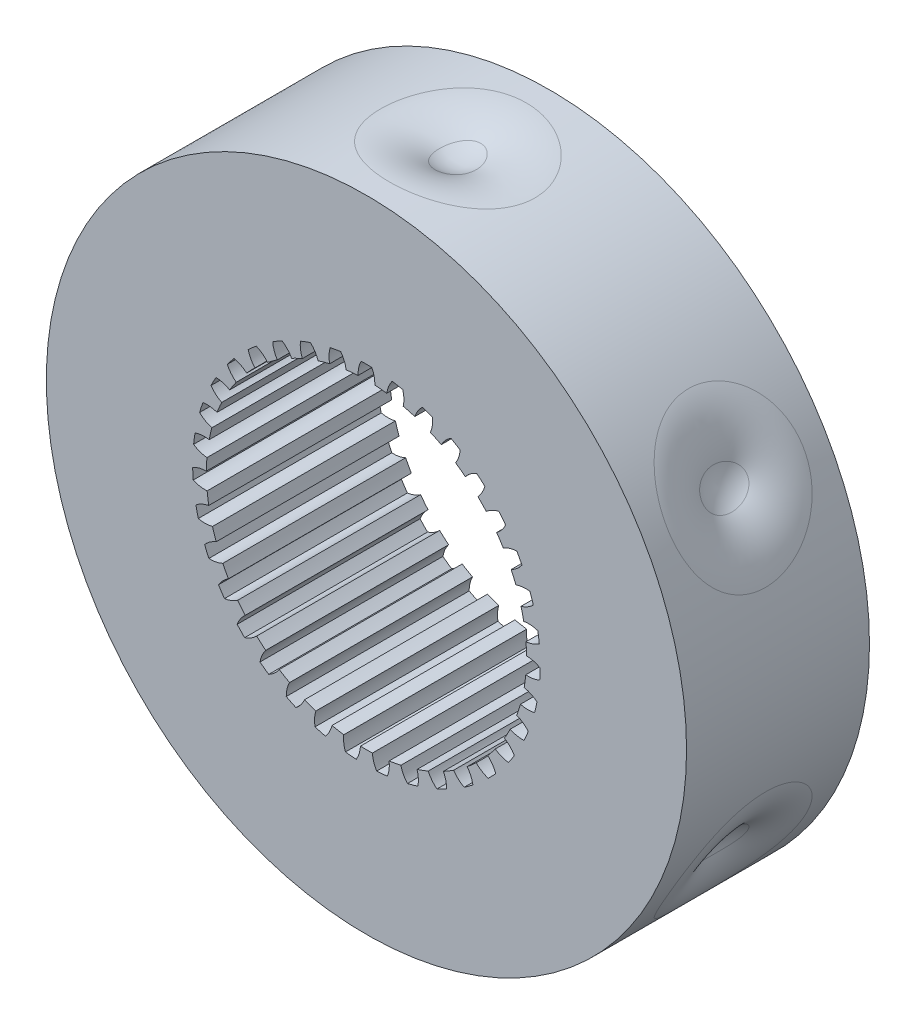
SolidWorks part; units mm, degrees
ref_plane "Front Plane" through (0, 0, 0) normal (0, 0, 1) x (1, 0, 0)
ref_plane "Top Plane" through (0, 0, 0) normal (0, 1, 0) x (1, 0, 0)
ref_plane "Right Plane" through (0, 0, 0) normal (1, 0, 0) x (0, 0, -1)
sketch "Sketch1" plane through (0, 0, 0) normal (0, 0, 1) x (1, 0, 0)
  circle A0 centre (0, 0) radius 35
  dimension "D1" = 70
extrude "Boss-Extrude1" add sketch "Sketch1" along normal mid plane 20
sketch "Sketch2" plane through (0, 0, 0) normal (0, 0, 1) x (1, 0, 0)
  line L0 (0, 0) -> (0, 38.6645) construction
  line L1 (0, 33) -> (0, 43)
  arc A0 (0, 33) -> (0, 43) centre (0, 38) ccw
  dimension "D2" = 10
  dimension "D1" = 38
revolve "Cut-Revolve1" cut sketch "Sketch2" angle 360 about L0
fillet "Fillet1" radius 10 1 edges at (-3.7349, 34.8001, -0.9006)
sketch "Sketch3" plane through (0, 0, -10) normal (0, 0, -1) x (-1, 0, 0)
  line L0 (0, 0) -> (0, 19.9196) construction
  arc A0 (-0.9159, 17.476) -> (-2.2193, 17.3587) centre (0, 0) ccw
  arc A1 (0.5906, 18.9908) -> (-0.5906, 18.9908) centre (0, 0) ccw
  arc A4 (-0.9159, 17.476) -> (-0.5906, 18.9908) centre (2.2552, 17.5875) cw
  arc A5 (0.9159, 17.476) -> (0.5906, 18.9908) centre (-2.2552, 17.5875) ccw
  arc A6 (3.9721, 18.5802) -> (2.8098, 18.7911) centre (0, 0) ccw
  arc A7 (2.2193, 17.3587) -> (2.8098, 18.7911) centre (5.3593, 16.9022) cw
  arc A8 (2.2193, 17.3587) -> (0.9159, 17.476) centre (0, 0) ccw
  arc A9 (4.0216, 17.0316) -> (3.9721, 18.5802) centre (0.9214, 17.7075) ccw
  arc A10 (7.2259, 17.5723) -> (6.1199, 17.9874) centre (0, 0) ccw
  arc A11 (5.2832, 16.6835) -> (6.1199, 17.9874) centre (8.2912, 15.6736) cw
  arc A12 (5.2832, 16.6835) -> (0, 17.5) centre (0, 0) ccw
  arc A13 (6.9981, 16.0398) -> (7.2259, 17.5723) centre (4.0684, 17.2584) ccw
  arc A14 (10.2474, 15.9997) -> (9.2333, 16.6056) centre (0, 0) ccw
  arc A15 (8.1772, 15.472) -> (9.2333, 16.6056) centre (10.9566, 13.9413) cw
  arc A16 (8.1772, 15.472) -> (-5.2832, 16.6835) centre (0, 0) ccw
  arc A17 (9.7497, 14.5325) -> (10.2474, 15.9997) centre (7.0846, 16.2547) ccw
  arc A18 (12.9396, 13.9128) -> (12.05, 14.6901) centre (0, 0) ccw
  arc A19 (10.8084, 13.7633) -> (12.05, 14.6901) centre (13.2698, 11.7608) cw
  arc A20 (10.8084, 13.7633) -> (-5.2832, 16.6835) centre (0, 0) ccw
  arc A21 (12.1879, 12.5581) -> (12.9396, 13.9128) centre (9.8731, 14.7284) ccw
  arc A22 (15.2159, 11.3788) -> (14.4794, 12.3024) centre (0, 0) ccw
  arc A23 (13.0923, 11.6122) -> (14.4794, 12.3024) centre (15.1566, 9.2024) cw
  arc A24 (13.0923, 11.6122) -> (-5.2832, 16.6835) centre (0, 0) ccw
  arc A25 (14.2343, 10.1801) -> (15.2159, 11.3788) centre (12.3443, 12.7288) ccw
  arc A26 (17.0031, 8.479) -> (16.4433, 9.5193) centre (0, 0) ccw
  arc A27 (14.9553, 9.0879) -> (16.4433, 9.5193) centre (16.5561, 6.3482) cw
  arc A28 (14.9553, 9.0879) -> (15.8233, 7.4748) centre (0, 0) ccw
  arc A29 (15.8233, 7.4748) -> (17.0031, 8.479) centre (14.4188, 10.3201) ccw
  arc A30 (18.2439, 5.3067) -> (17.8788, 6.4302) centre (0, 0) ccw
  arc A31 (16.3377, 6.2714) -> (17.8788, 6.4302) centre (17.4236, 3.29) cw
  arc A32 (16.3377, 6.2714) -> (16.9037, 4.5293) centre (0, 0) ccw
  arc A33 (16.9037, 4.5293) -> (18.2439, 5.3067) centre (16.0298, 7.5797) ccw
  arc A34 (18.8982, 1.9639) -> (18.7397, 3.1345) centre (0, 0) ccw
  arc A35 (17.1949, 3.2535) -> (18.7397, 3.1345) centre (17.731, 0.126) cw
  arc A36 (17.1949, 3.2535) -> (17.4408, 1.4383) centre (0, 0) ccw
  arc A37 (17.4408, 1.4383) -> (18.8982, 1.9639) centre (17.1256, 4.5956) ccw
  arc A38 (18.9452, -1.4421) -> (18.9982, -0.262) centre (0, 0) ccw
  arc A39 (17.4995, 0.1309) -> (18.9982, -0.262) centre (17.4686, -3.042) cw
  arc A40 (17.4995, 0.1309) -> (17.4173, -1.699) centre (0, 0) ccw
  arc A41 (17.4173, -1.699) -> (18.9452, -1.4421) centre (17.671, 1.4639) ccw
  arc A42 (18.3832, -4.8017) -> (18.6461, -3.65) centre (0, 0) ccw
  arc A43 (17.2417, -2.9959) -> (18.6461, -3.65) centre (16.6447, -6.1123) cw
  arc A44 (17.2417, -2.9959) -> (16.8341, -4.7817) centre (0, 0) ccw
  arc A45 (16.8341, -4.7817) -> (18.3832, -4.8017) centre (17.6484, -1.7149) ccw
  arc A46 (17.2304, -8.007) -> (17.6947, -6.9207) centre (0, 0) ccw
  arc A47 (16.4296, -6.0263) -> (17.6947, -6.9207) centre (15.2858, -8.9861) cw
  arc A48 (16.4296, -6.0263) -> (15.7097, -7.7107) centre (0, 0) ccw
  arc A49 (15.7097, -7.7107) -> (17.2304, -8.007) centre (17.0585, -4.8386) ccw
  arc A50 (15.5238, -10.9549) -> (16.1746, -9.969) centre (0, 0) ccw
  arc A51 (15.0896, -8.8631) -> (16.1746, -9.969) centre (13.4357, -11.571) cw
  arc A52 (15.0896, -8.8631) -> (14.0805, -10.3919) centre (0, 0) ccw
  arc A53 (14.0805, -10.3919) -> (15.5238, -10.9549) centre (15.9204, -7.8067) ccw
  arc A54 (13.3183, -13.5508) -> (14.1346, -12.6969) centre (0, 0) ccw
  arc A55 (13.2645, -11.415) -> (14.1346, -12.6969) centre (11.1536, -13.7841) cw
  arc A56 (13.2645, -11.415) -> (11.9986, -12.739) centre (0, 0) ccw
  arc A57 (11.9986, -12.739) -> (13.3183, -13.5508) centre (14.2706, -10.524) ccw
  arc A58 (10.6847, -15.7111) -> (11.6404, -15.0167) centre (0, 0) ccw
  arc A59 (11.0131, -13.6001) -> (11.6404, -15.0167) centre (8.5132, -15.5542) cw
  arc A60 (11.0131, -13.6001) -> (9.5312, -14.6767) centre (0, 0) ccw
  arc A61 (9.5312, -14.6767) -> (10.6847, -15.7111) centre (12.1622, -12.903) ccw
  arc A62 (7.7076, -17.3664) -> (8.772, -16.8539) centre (0, 0) ccw
  arc A63 (8.4077, -15.348) -> (8.772, -16.8539) centre (5.599, -16.8243) cw
  arc A64 (8.4077, -15.348) -> (6.7574, -16.1427) centre (0, 0) ccw
  arc A65 (6.7574, -16.1427) -> (7.7076, -17.3664) centre (9.6628, -14.8673) ccw
  arc A66 (4.4829, -18.4636) -> (5.6216, -18.1493) centre (0, 0) ccw
  arc A67 (5.5321, -16.6026) -> (5.6216, -18.1493) centre (2.505, -17.5537) cw
  arc A68 (5.5321, -16.6026) -> (3.7664, -17.0899) centre (0, 0) ccw
  arc A69 (3.7664, -17.0899) -> (4.4829, -18.4636) centre (6.8529, -16.3537) ccw
  arc A70 (1.1141, -18.9673) -> (2.2906, -18.8614) centre (0, 0) ccw
  arc A71 (2.4787, -17.3236) -> (2.2906, -18.8614) centre (-0.6696, -17.7188) cw
  arc A72 (2.4787, -17.3236) -> (0.6543, -17.4878) centre (0, 0) ccw
  arc A73 (0.6543, -17.4878) -> (1.1141, -18.9673) centre (3.8227, -17.3145) ccw
  arc A74 (-2.2906, -18.8614) -> (-1.1141, -18.9673) centre (0, 0) ccw
  arc A75 (-0.6543, -17.4878) -> (-1.1141, -18.9673) centre (-3.8227, -17.3145) cw
  arc A76 (-0.6543, -17.4878) -> (-2.4787, -17.3236) centre (0, 0) ccw
  arc A77 (-2.4787, -17.3236) -> (-2.2906, -18.8614) centre (0.6696, -17.7188) ccw
  arc A78 (-5.6216, -18.1493) -> (-4.4829, -18.4636) centre (0, 0) ccw
  arc A79 (-3.7664, -17.0899) -> (-4.4829, -18.4636) centre (-6.8529, -16.3537) cw
  arc A80 (-3.7664, -17.0899) -> (-5.5321, -16.6026) centre (0, 0) ccw
  arc A81 (-5.5321, -16.6026) -> (-5.6216, -18.1493) centre (-2.505, -17.5537) ccw
  arc A82 (-8.772, -16.8539) -> (-7.7076, -17.3664) centre (0, 0) ccw
  arc A83 (-6.7574, -16.1427) -> (-7.7076, -17.3664) centre (-9.6628, -14.8673) cw
  arc A84 (-6.7574, -16.1427) -> (-8.4077, -15.348) centre (0, 0) ccw
  arc A85 (-8.4077, -15.348) -> (-8.772, -16.8539) centre (-5.599, -16.8243) ccw
  arc A86 (-11.6404, -15.0167) -> (-10.6847, -15.7111) centre (0, 0) ccw
  arc A87 (-9.5312, -14.6767) -> (-10.6847, -15.7111) centre (-12.1622, -12.903) cw
  arc A88 (-9.5312, -14.6767) -> (-11.0131, -13.6001) centre (0, 0) ccw
  arc A89 (-11.0131, -13.6001) -> (-11.6404, -15.0167) centre (-8.5132, -15.5542) ccw
  arc A90 (-14.1346, -12.6969) -> (-13.3183, -13.5508) centre (0, 0) ccw
  arc A91 (-11.9986, -12.739) -> (-13.3183, -13.5508) centre (-14.2706, -10.524) cw
  arc A92 (-11.9986, -12.739) -> (-13.2645, -11.415) centre (0, 0) ccw
  arc A93 (-13.2645, -11.415) -> (-14.1346, -12.6969) centre (-11.1536, -13.7841) ccw
  arc A94 (-16.1746, -9.969) -> (-15.5238, -10.9549) centre (0, 0) ccw
  arc A95 (-14.0805, -10.3919) -> (-15.5238, -10.9549) centre (-15.9204, -7.8067) cw
  arc A96 (-14.0805, -10.3919) -> (-15.0896, -8.8631) centre (0, 0) ccw
  arc A97 (-15.0896, -8.8631) -> (-16.1746, -9.969) centre (-13.4357, -11.571) ccw
  arc A98 (-17.6947, -6.9207) -> (-17.2304, -8.007) centre (0, 0) ccw
  arc A99 (-15.7097, -7.7107) -> (-17.2304, -8.007) centre (-17.0585, -4.8386) cw
  arc A100 (-15.7097, -7.7107) -> (-16.4296, -6.0263) centre (0, 0) ccw
  arc A101 (-16.4296, -6.0263) -> (-17.6947, -6.9207) centre (-15.2858, -8.9861) ccw
  arc A102 (-18.6461, -3.65) -> (-18.3832, -4.8017) centre (0, 0) ccw
  arc A103 (-16.8341, -4.7817) -> (-18.3832, -4.8017) centre (-17.6484, -1.7149) cw
  arc A104 (-16.8341, -4.7817) -> (-17.2417, -2.9959) centre (0, 0) ccw
  arc A105 (-17.2417, -2.9959) -> (-18.6461, -3.65) centre (-16.6447, -6.1123) ccw
  arc A106 (-18.9982, -0.262) -> (-18.9452, -1.4421) centre (0, 0) ccw
  arc A107 (-17.4173, -1.699) -> (-18.9452, -1.4421) centre (-17.671, 1.4639) cw
  arc A108 (-17.4173, -1.699) -> (-17.4995, 0.1309) centre (0, 0) ccw
  arc A109 (-17.4995, 0.1309) -> (-18.9982, -0.262) centre (-17.4686, -3.042) ccw
  arc A110 (-18.7397, 3.1345) -> (-18.8982, 1.9639) centre (0, 0) ccw
  arc A111 (-17.4408, 1.4383) -> (-18.8982, 1.9639) centre (-17.1256, 4.5956) cw
  arc A112 (-17.4408, 1.4383) -> (-17.1949, 3.2535) centre (0, 0) ccw
  arc A113 (-17.1949, 3.2535) -> (-18.7397, 3.1345) centre (-17.731, 0.126) ccw
  arc A114 (-17.8788, 6.4302) -> (-18.2439, 5.3067) centre (0, 0) ccw
  arc A115 (-16.9037, 4.5293) -> (-18.2439, 5.3067) centre (-16.0298, 7.5797) cw
  arc A116 (-16.9037, 4.5293) -> (-16.3377, 6.2714) centre (0, 0) ccw
  arc A117 (-16.3377, 6.2714) -> (-17.8788, 6.4302) centre (-17.4236, 3.29) ccw
  arc A118 (-16.4433, 9.5193) -> (-17.0031, 8.479) centre (0, 0) ccw
  arc A119 (-15.8233, 7.4748) -> (-17.0031, 8.479) centre (-14.4188, 10.3201) cw
  arc A120 (-15.8233, 7.4748) -> (-14.9553, 9.0879) centre (0, 0) ccw
  arc A121 (-14.9553, 9.0879) -> (-16.4433, 9.5193) centre (-16.5561, 6.3482) ccw
  arc A122 (-14.4794, 12.3024) -> (-15.2159, 11.3788) centre (0, 0) ccw
  arc A123 (-14.2343, 10.1801) -> (-15.2159, 11.3788) centre (-12.3443, 12.7288) cw
  arc A124 (-14.2343, 10.1801) -> (-13.0923, 11.6122) centre (0, 0) ccw
  arc A125 (-13.0923, 11.6122) -> (-14.4794, 12.3024) centre (-15.1566, 9.2024) ccw
  arc A126 (-12.05, 14.6901) -> (-12.9396, 13.9128) centre (0, 0) ccw
  arc A127 (-12.1879, 12.5581) -> (-12.9396, 13.9128) centre (-9.8731, 14.7284) cw
  arc A128 (-12.1879, 12.5581) -> (-10.8084, 13.7633) centre (0, 0) ccw
  arc A129 (-10.8084, 13.7633) -> (-12.05, 14.6901) centre (-13.2698, 11.7608) ccw
  arc A130 (-9.2333, 16.6056) -> (-10.2474, 15.9997) centre (0, 0) ccw
  arc A131 (-9.7497, 14.5325) -> (-10.2474, 15.9997) centre (-7.0846, 16.2547) cw
  arc A132 (-9.7497, 14.5325) -> (-8.1772, 15.472) centre (0, 0) ccw
  arc A133 (-8.1772, 15.472) -> (-9.2333, 16.6056) centre (-10.9566, 13.9413) ccw
  arc A134 (-6.1199, 17.9874) -> (-7.2259, 17.5723) centre (0, 0) ccw
  arc A135 (-6.9981, 16.0398) -> (-7.2259, 17.5723) centre (-4.0684, 17.2584) cw
  arc A136 (-6.9981, 16.0398) -> (-5.2832, 16.6835) centre (0, 0) ccw
  arc A137 (-5.2832, 16.6835) -> (-6.1199, 17.9874) centre (-8.2912, 15.6736) ccw
  arc A138 (-2.8098, 18.7911) -> (-3.9721, 18.5802) centre (0, 0) ccw
  arc A139 (-4.0216, 17.0316) -> (-3.9721, 18.5802) centre (-0.9214, 17.7075) cw
  arc A140 (-4.0216, 17.0316) -> (-2.2193, 17.3587) centre (0, 0) ccw
  arc A141 (-2.2193, 17.3587) -> (-2.8098, 18.7911) centre (-5.3593, 16.9022) ccw
  arc A142 (0, 17.5) -> (4.0216, 17.0316) centre (0, 0) ccw
  arc A143 (-0.9159, 17.476) -> (6.9981, 16.0398) centre (0, 0) ccw
  arc A144 (-4.0216, 17.0316) -> (0.9159, 17.476) centre (0, 0) ccw
  arc A145 (-6.9981, 16.0398) -> (9.7497, 14.5325) centre (0, 0) ccw
  arc A146 (-6.9981, 16.0398) -> (12.1879, 12.5581) centre (0, 0) ccw
  arc A147 (-6.9981, 16.0398) -> (14.2343, 10.1801) centre (0, 0) ccw
  point P215 (0, 0)
  dimension "D1" = 35
  dimension "D3" = 38
  dimension "D2" = 35
extrude "Cut-Extrude1" cut sketch "Sketch3" against normal through all contours A28 A32 A24 A20 A16 A12 A8 A0 A136 A132 A128 A124 A120 A116 A112 A108 A104 A100 A96 A92 A88 A84 A80 A76 A72 | A28 A137 A134 A135 | A128 A133 A130 A131 | A124 A129 A126 A127 | A120 A125 A122 A123 | A116 A121 A118 A119 | A112 A117 A114 A115 | A108 A113 A110 A111 | A104 A109 A106 A107 | A100 A105 A102 A103 | A96 A101 A98 A99 | A92 A97 A94 A95 | A88 A93 A90 A91 | A84 A89 A86 A87 | A80 A85 A82 A83 | A64 A69 A66 A67 | A60 A65 A62 A63 | A56 A61 A58 A59 | A52 A57 A54 A55 | A48 A53 A50 A51 | A44 A49 A46 A47 | A40 A45 A42 A43 | A36 A41 A38 A39 | A28 A33 A30 A31 | A32 A29 A26 A27 | A76 A81 A78 A79 | A72 A77 A74 A75 | A68 A73 A70 A71 | A28 A25 A22 A23 | A24 A21 A18 A19 | A20 A17 A14 A15 | A16 A13 A10 A11 | A12 A9 A6 A7 | L0 A12 A5 A1 | A16 A141 A138 A139 | A16 L0 A1 A4 | A35 A34 A37 A36 region at (0.4155, 18.1946, -10) region at (-0.4155, 18.1946, -10) region at (-0.4451, 16.9992, -10) region at (-3.2488, 17.9022, -10) region at (3.2488, 17.9022, -10) region at (-6.3931, 17.0345, -10) region at (6.3931, 17.0345, -10) region at (-9.332, 15.6192, -10) region at (9.332, 15.6192, -10) region at (-11.971, 13.7019, -10) region at (11.971, 13.7019, -10) region at (-14.2251, 11.3442, -10) region at (14.2251, 11.3442, -10) region at (-16.0221, 8.6219, -10) region at (16.0221, 8.6219, -10) region at (-17.3041, 5.6225, -10) region at (17.3041, 5.6225, -10) region at (18.03, 2.4423, -10) region at (-18.1763, -0.8163, -10) region at (18.1763, -0.8163, -10) region at (-17.7385, -4.0487, -10) region at (17.7385, -4.0487, -10) region at (-16.7305, -7.1509, -10) region at (16.7305, -7.1509, -10) region at (-15.1848, -10.0234, -10) region at (15.1848, -10.0234, -10) region at (-13.151, -12.5736, -10) region at (13.151, -12.5736, -10) region at (-10.6945, -14.7198, -10) region at (10.6945, -14.7198, -10) region at (-7.8944, -16.3928, -10) region at (7.8944, -16.3928, -10) region at (-4.8404, -17.539, -10) region at (4.8404, -17.539, -10) region at (-1.631, -18.1214, -10) region at (1.631, -18.1214, -10)
pattern_circular "CirPattern1" count 6 over 360 about axis through (0, 0, -10) along (0, 0, 1) of "Fillet1", "Cut-Revolve1"
